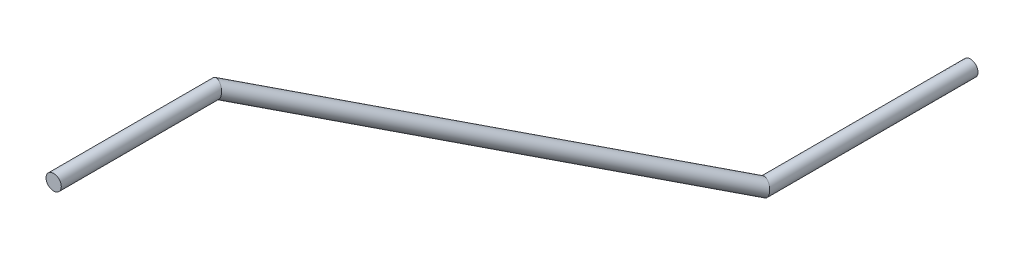
SolidWorks part; units mm, degrees
ref_plane "Front Plane" through (0, 0, 0) normal (0, 0, 1) x (1, 0, 0)
ref_plane "Top Plane" through (0, 0, 0) normal (0, 1, 0) x (1, 0, 0)
ref_plane "Right Plane" through (0, 0, 0) normal (1, 0, 0) x (0, 0, -1)
sketch3d "Route through both anchors"
  line L0 (15, -25.9808, -16.2) -> (15, -25.9808, 0)
  line L1 (15, -25.9808, 0) -> (-2.0875, -14.854, 25.9599)
  line L2 (-2.0875, -14.854, 25.9599) -> (-2.0875, -14.854, 38.7099)
sweep "Round TPU cord - 1.2 mm" add path "Route through both anchors" circular profile diameter 1.2 parameters "D3"=1.2
